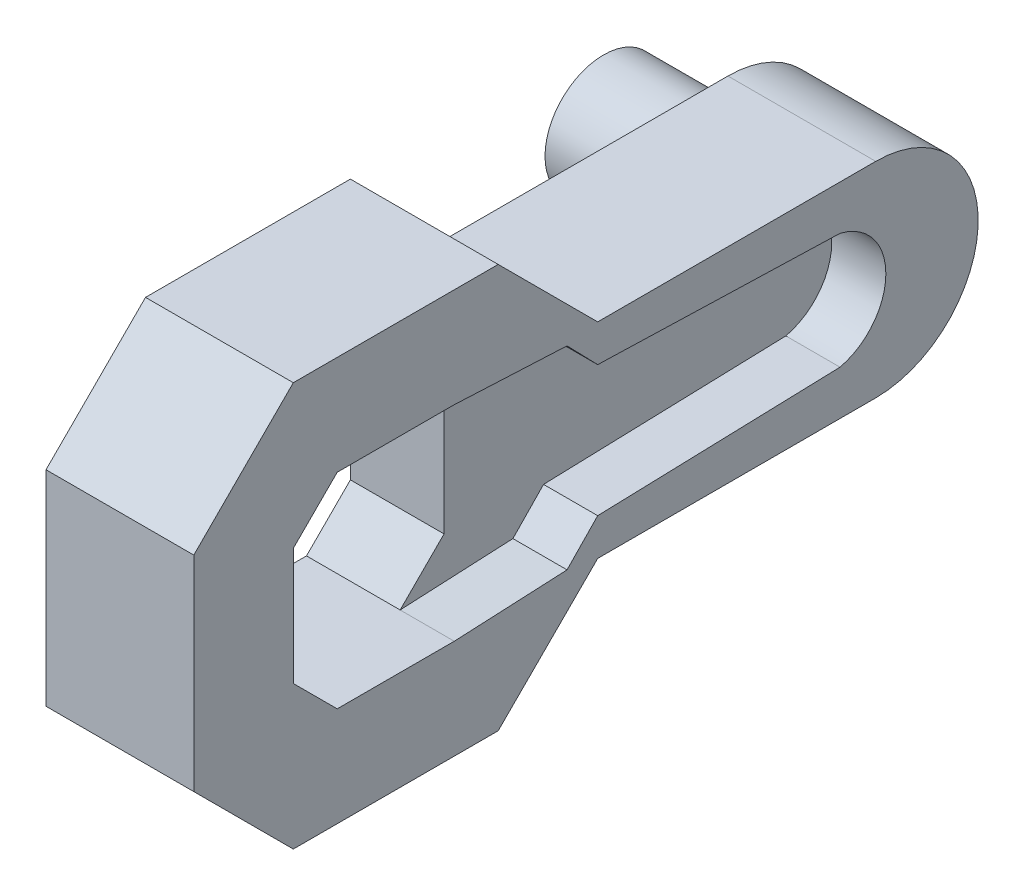
SolidWorks part; units mm, degrees
ref_plane "Front" through (0, 0, 0) normal (0, 0, 1) x (1, 0, 0)
ref_plane "Top" through (0, 0, 0) normal (0, 1, 0) x (1, 0, 0)
ref_plane "Right" through (0, 0, 0) normal (1, 0, 0) x (0, 0, -1)
sketch "Sketch1" plane through (0, 0, 0) normal (1, 0, 0) x (0, 0, -1)
  line L0 (6.9, 3.5) -> (6.9, 6.9)
  line L1 (-3.5, -3.5) -> (3.5, -3.5)
  line L2 (-3.5, -3.5) -> (-3.5, 3.5)
  line L3 (-3.5, 3.5) -> (3.5, 3.5)
  line L4 (3.5, -3.5) -> (3.5, 3.5)
  line L5 (-3.5, -3.5) -> (3.5, 3.5) construction
  line L6 (-3.5, 3.5) -> (3.5, -3.5) construction
  line L7 (-6.9, -6.9) -> (6.9, -6.9)
  line L8 (-6.9, -6.9) -> (-6.9, 6.9)
  line L9 (-6.9, 6.9) -> (6.9, 6.9)
  line L10 (6.9, -6.9) -> (6.9, -3.5)
  line L11 (-6.9, -6.9) -> (6.9, 6.9) construction
  line L12 (-6.9, 6.9) -> (6.9, -6.9) construction
  line L13 (6.9, 3.5) -> (19.9, 3.5)
  line L15 (6.9, -3.5) -> (19.9, -3.5)
  line L16 (19.9, 3.5) -> (19.9, -3.5)
  point P0 (0, 0)
  point P6 (0, 0)
  point P19 (12.3, 0)
  dimension "D1" = 7
  dimension "D2" = 7
  dimension "D3" = 13.8
  dimension "D4" = 13.8
  dimension "D5" = 13
  dimension "D8" = 12.3
extrude "Boss-Extrude1" add sketch "Sketch1" along normal blind 3.2
chamfer "Chamfer1" distance 1.5 angle 45 4 edges at (1.6, 3.5, -3.5) (1.6, -3.5, -3.5) (1.6, -3.5, 3.5) (1.6, 3.5, 3.5)
fillet "Fillet1" radius 3.5 2 edges at (1.6, -3.5, -19.9) (1.6, 3.5, -19.9)
chamfer "Chamfer2" distance 3.4 angle 45 4 edges at (1.6, -6.9, -6.9) (1.6, -6.9, 6.9) (1.6, 6.9, 6.9) (1.6, 6.9, -6.9)
sketch "Sketch2" plane through (3.2, 0, 0) normal (1, 0, 0) x (0, 0, -1)
  circle A0 centre (0, 0) radius 4.0311 construction
sketch "Sketch3" plane through (0, 0, 0) normal (-1, 0, 0) x (0, 0, 1)
  circle A0 centre (-16.4, 0) radius 2
  dimension "D1" = 4
extrude "Boss-Extrude2" add sketch "Sketch3" along normal blind 4.25
sketch "Sketch4" plane through (3.2, 0, 0) normal (1, 0, 0) x (0, 0, -1)
  line L2 (6.9, 2.2346) -> (15.179, 1.9798)
  line L3 (6.9, -2.2346) -> (15.179, -1.9798)
  line L5 (1.6584, -2.3959) -> (15.179, -1.9798) construction
  line L6 (1.592, -2.1978) -> (15.1521, -1.7805) construction
  line L7 (1.5915, 2.1978) -> (15.1521, 1.7805) construction
  line L8 (1.6578, 2.3959) -> (15.179, 1.9798) construction
  line L9 (5.8529, 3.3143) -> (15.3057, 3.0234)
  line L10 (5.8529, -3.3143) -> (15.3057, -3.0234)
  line L12 (6.9, 2.2346) -> (5.8529, 3.3143)
  line L13 (6.9, -2.2346) -> (5.8529, -3.3143)
  line L14 (3.5, -2) -> (3.5, 2) construction
  line L15 (6.9, 2.2346) -> (6.9, -2.2346) construction
  line L16 (5.8529, 3.3143) -> (5.8529, -3.3143) construction
  arc A2 (15.1521, -1.7805) -> (15.1521, 1.7805) centre (14.7117, 0) ccw construction
  arc A4 (15.179, -1.9798) -> (15.179, 1.9798) centre (14.7117, 0) ccw
  arc A6 (1.6578, 2.3959) -> (1.6584, -2.3959) centre (0.0001, -0.0002) ccw construction
  arc A7 (1.5915, 2.1978) -> (1.592, -2.1978) centre (0.0001, -0.0002) ccw construction
  arc A8 (15.3057, -3.0234) -> (15.3057, 3.0234) centre (14.7117, 0) ccw
  point P31 (3.5, 0)
  dimension "D2" = 0.2
extrude "Boss-Extrude3" add sketch "Sketch4" along normal blind 1.85
sketch "Sketch5" plane through (3.2, 0, 0) normal (1, 0, 0) x (0, 0, -1)
  line L0 (5.8529, 3.3143) -> (2, 3.5)
  line L1 (5.8529, -3.3143) -> (2, -3.5)
  line L2 (2, -3.5) -> (-2, -3.5)
  line L3 (-2, -3.5) -> (-3.5, -2)
  line L4 (-3.5, -2) -> (-3.5, 2)
  line L9 (-3.5, -6.9) -> (3.5, -6.9)
  line L10 (3.5, -6.9) -> (6.9, -3.5)
  line L11 (6.9, -3.5) -> (16.4, -3.5)
  line L12 (16.4, 3.5) -> (6.9, 3.5)
  line L13 (6.9, 3.5) -> (3.5, 6.9)
  line L14 (3.5, 6.9) -> (-3.5, 6.9)
  line L15 (-3.5, 6.9) -> (-6.9, 3.5)
  line L16 (-6.9, 3.5) -> (-6.9, -3.5)
  line L17 (-6.9, -3.5) -> (-3.5, -6.9)
  line L18 (-3.5, -6.9) -> (3.5, -6.9)
  line L19 (3.5, -6.9) -> (6.9, -3.5)
  line L20 (6.9, -3.5) -> (16.4, -3.5)
  line L21 (16.4, 3.5) -> (6.9, 3.5)
  line L22 (6.9, 3.5) -> (3.5, 6.9)
  line L23 (3.5, 6.9) -> (-3.5, 6.9)
  line L24 (-3.5, 6.9) -> (-6.9, 3.5)
  line L25 (-6.9, 3.5) -> (-6.9, -3.5)
  line L26 (-6.9, -3.5) -> (-3.5, -6.9)
  arc A2 (16.4, -3.5) -> (19.9, 0) centre (16.4, 0) ccw
  arc A3 (19.9, 0) -> (16.4, 3.5) centre (16.4, 0) ccw
  arc A4 (16.4, -3.5) -> (19.9, 0) centre (16.4, 0) ccw
  arc A5 (19.9, 0) -> (16.4, 3.5) centre (16.4, 0) ccw
  line M16 (-3.5, -6.9) -> (3.5, -6.9)
  line M17 (3.5, -6.9) -> (6.9, -3.5)
  line M18 (6.9, -3.5) -> (16.4, -3.5)
  arc M19 (16.4, -3.5) -> (19.9, 0) centre (16.4, 0) ccw
  arc M20 (19.9, 0) -> (16.4, 3.5) centre (16.4, 0) ccw
  line M21 (16.4, 3.5) -> (6.9, 3.5)
  line M22 (6.9, 3.5) -> (3.5, 6.9)
  line M23 (3.5, 6.9) -> (-3.5, 6.9)
  line M24 (-3.5, 6.9) -> (-6.9, 3.5)
  line M25 (-6.9, 3.5) -> (-6.9, -3.5)
  line M26 (-6.9, -3.5) -> (-3.5, -6.9)
  line M27 (-2, 3.5) -> (2, 3.5)
  line M31 (2, -3.5) -> (-2, -3.5)
  line M32 (-2, -3.5) -> (-3.5, -2)
  line M33 (-3.5, -2) -> (-3.5, 2)
  line M34 (-3.5, 2) -> (-2, 3.5)
  line M41 (5.8529, 3.3143) -> (15.3057, 3.0234)
  arc M42 (15.3057, 3.0234) -> (15.3057, -3.0234) centre (14.7117, 0) cw
  line M43 (15.3057, -3.0234) -> (5.8529, -3.3143)
  dimension "D1" = 0
extrude "Boss-Extrude4" add sketch "Sketch5" along normal blind 1.85 contours L1 L0 M26 M16 M17 M18 M19 M20 M21 M22 M23 M24 M25 M43 M31 M32 M33 M34 M27 M41 M42 region at (3.2, -4.9868, 4.9868)
